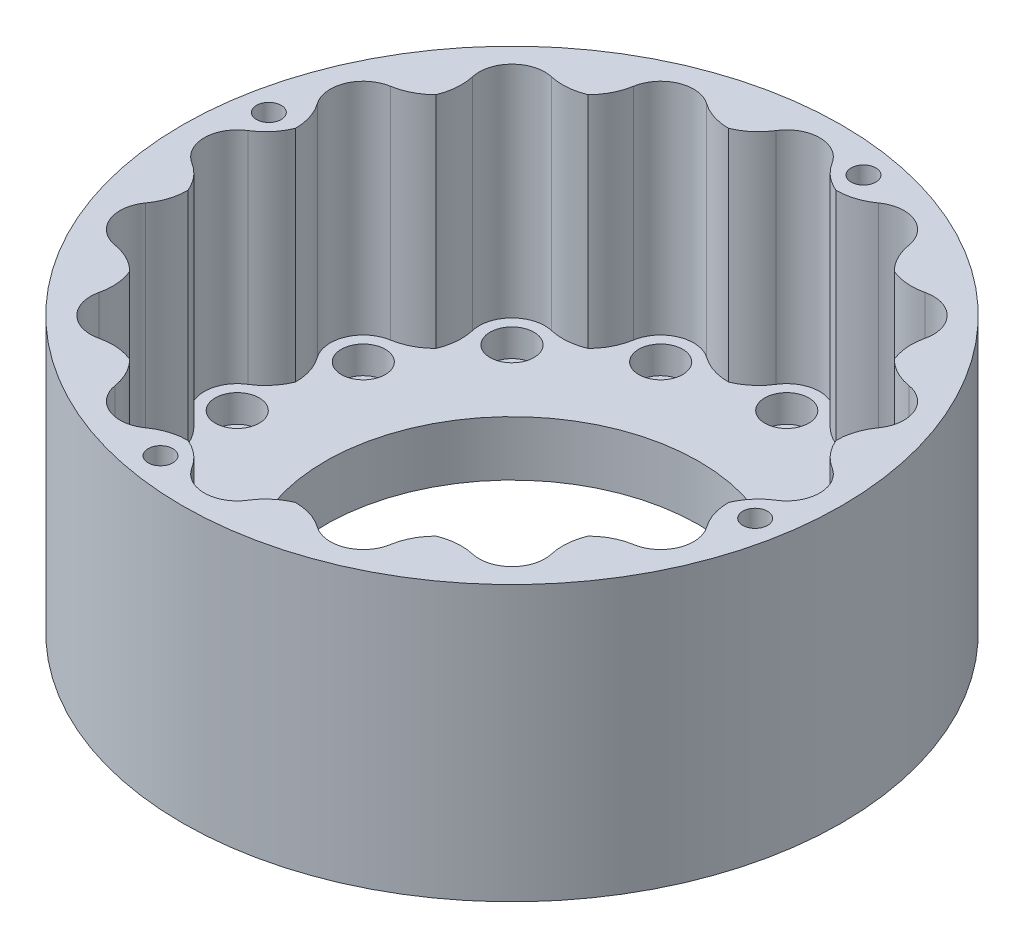
SolidWorks part; units mm, degrees
ref_plane "Front Plane" through (0, 0, 0) normal (0, 0, 1) x (1, 0, 0)
ref_plane "Top Plane" through (0, 0, 0) normal (0, 1, 0) x (1, 0, 0)
ref_plane "Right Plane" through (0, 0, 0) normal (1, 0, 0) x (0, 0, -1)
sketch "Sketch1" plane through (0, 0, 0) normal (0, 1, 0) x (1, 0, 0)
  arc A0 (-50.0283, 13.4631) -> (-51.515, 5.9892) centre (-1.875, 0) ccw
  arc A1 (4.1142, 49.64) -> (-7.8642, 49.64) centre (-1.875, 50) ccw
  arc A2 (-16.6515, 42.0695) -> (-16.6233, 42.0995) centre (-21.0092, 46.194) ccw
  arc A3 (-32.7408, 39.3358) -> (-41.2108, 30.8658) centre (-37.2303, 35.3553) ccw
  arc A4 (-45.4444, 24.5297) -> (-50.0283, 13.4631) centre (-48.069, 19.1342) ccw
  arc A5 (-51.515, 5.9892) -> (-51.515, -5.9892) centre (-51.875, 0) ccw
  arc A6 (-50.0283, -13.4631) -> (-45.4444, -24.5297) centre (-48.069, -19.1342) ccw
  arc A7 (-41.2108, -30.8658) -> (-32.7408, -39.3358) centre (-37.2303, -35.3553) ccw
  arc A8 (-26.4047, -43.5694) -> (-15.3381, -48.1533) centre (-21.0092, -46.194) ccw
  arc A9 (-7.8642, -49.64) -> (4.1142, -49.64) centre (-1.875, -50) ccw
  arc A10 (11.5881, -48.1533) -> (22.6547, -43.5694) centre (17.2592, -46.194) ccw
  arc A11 (28.9908, -39.3358) -> (37.4608, -30.8658) centre (33.4803, -35.3553) ccw
  arc A12 (40.4731, -14.5288) -> (40.4074, -14.5845) centre (44.319, -19.1342) ccw
  arc A13 (47.765, -5.9892) -> (47.765, 5.9892) centre (48.125, 0) ccw
  arc A14 (40.4074, 14.5845) -> (40.4731, 14.5288) centre (44.319, 19.1342) ccw
  arc A15 (37.4608, 30.8658) -> (28.9908, 39.3358) centre (33.4803, 35.3553) ccw
  arc A16 (22.6547, 43.5694) -> (11.5881, 48.1533) centre (17.2592, 46.194) ccw
  circle A17 centre (-1.875, 0) radius 60
  arc A18 (-41.2108, 30.8658) -> (-45.4444, 24.5297) centre (-1.875, 0) ccw
  arc A19 (-26.4047, 43.5694) -> (-32.7408, 39.3358) centre (-1.875, 0) ccw
  arc A20 (-15.3381, 48.1533) -> (-26.4047, 43.5694) centre (-21.0092, 46.194) ccw
  arc A21 (-7.8642, 49.64) -> (-15.3381, 48.1533) centre (-1.875, 0) ccw
  arc A22 (11.5881, 48.1533) -> (4.1142, 49.64) centre (-1.875, 0) ccw
  arc A23 (28.9908, 39.3358) -> (22.6547, 43.5694) centre (-1.875, 0) ccw
  arc A24 (41.6944, 24.5297) -> (37.4608, 30.8658) centre (-1.875, 0) ccw
  arc A25 (46.2783, 13.4631) -> (41.6944, 24.5297) centre (44.319, 19.1342) ccw
  arc A26 (46.2783, -13.4631) -> (47.765, -5.9892) centre (-1.875, 0) ccw
  arc A27 (41.6944, -24.5297) -> (46.2783, -13.4631) centre (44.319, -19.1342) ccw
  arc A28 (37.4608, -30.8658) -> (41.6944, -24.5297) centre (-1.875, 0) ccw
  arc A29 (-51.515, -5.9892) -> (-50.0283, -13.4631) centre (-1.875, 0) ccw
  arc A30 (-45.4444, -24.5297) -> (-41.2108, -30.8658) centre (-1.875, 0) ccw
  arc A31 (-32.7408, -39.3358) -> (-26.4047, -43.5694) centre (-1.875, 0) ccw
  arc A32 (-15.3381, -48.1533) -> (-7.8642, -49.64) centre (-1.875, 0) ccw
  arc A33 (-16.6233, -42.0995) -> (-16.6515, -42.0695) centre (-21.0092, -46.194) ccw
  arc A34 (4.1142, -49.64) -> (11.5881, -48.1533) centre (-1.875, 0) ccw
  arc A35 (22.6547, -43.5694) -> (28.9908, -39.3358) centre (-1.875, 0) ccw
  arc A36 (47.765, 5.9892) -> (46.2783, 13.4631) centre (-1.875, 0) ccw
  spline S0 degree 4 poles (44.0747, 11.4987) (44.2543, 11.2167) (44.5698, 10.6242) (44.9021, 9.6808) (45.0642, 8.3642) (44.9446, 7.1282) (44.593, 6.0249) (44.1211, 5.1947) (43.695, 4.5754) (43.3564, 4.0472) (43.0998, 3.6163) (42.8821, 3.198) (42.6994, 2.7973) (42.5503, 2.4153) (42.4301, 2.0557) (42.3415, 1.7357) (42.2778, 1.4587) (42.224, 1.1791) (42.1875, 0.9457) (42.1595, 0.7089) (42.1421, 0.4978) (42.1336, 0.3578) (42.1278, 0.2085) (42.1243, 0.037) (42.1247, -0.0678) (42.1293, -0.2634) (42.1379, -0.4367) (42.15, -0.5999) (42.1691, -0.7936) (42.1974, -1.0101) (42.2414, -1.2799) (42.3074, -1.6012) (42.4037, -1.9716) (42.5387, -2.3877) (42.6983, -2.7948) (42.8796, -3.1931) (43.1366, -3.6835) (43.482, -4.2594) (43.9287, -4.9065) (44.4091, -5.6745) (44.8007, -6.6105) (45.0295, -7.7093) (45.0295, -8.9484) (44.7352, -10.2696) (44.1902, -11.4212) (43.4619, -12.3657) (42.6206, -13.0778) (41.7593, -13.602) (40.7824, -14.2408) (39.77, -15.1062) (38.838, -16.2841) (38.1405, -17.7977) (37.8498, -19.2831) (37.8586, -20.6377) (38.0279, -21.8199) (38.2279, -22.8394) (38.2788, -23.9779) (38.0615, -25.1966) (37.5489, -26.4121) (36.7247, -27.5436) (35.7476, -28.3911) (34.706, -28.96) (33.6586, -29.2738) (32.6702, -29.405) (31.5286, -29.5836) (30.2595, -29.9481) (28.9262, -30.6268) (27.659, -31.7106) (26.7717, -32.9447) (26.2118, -34.1914) (25.9145, -35.2243) (25.7304, -35.9895) (25.5039, -36.7438) (25.1586, -37.555) (24.5413, -38.4785) (23.5696, -39.3957) (22.3328, -40.1097) (21.0527, -40.4927) (19.9443, -40.5655) (19.0691, -40.4589) (18.3026, -40.2779) (17.5479, -40.0547) (16.5047, -39.7958) (15.1451, -39.6573) (13.6327, -39.8087) (12.0605, -40.3642) (10.8061, -41.1795) (9.8558, -42.0964) (9.1304, -42.9957) (8.5226, -43.7861) (7.7271, -44.5363) (6.7136, -45.1539) (5.4911, -45.5763) (4.0991, -45.7244) (2.7902, -45.5605) (1.6261, -45.1394) (0.6656, -44.526) (-0.1173, -43.8431) (-1.0565, -43.1053) (-2.2252, -42.4205) (-3.657, -41.9295) (-5.3166, -41.7767) (-6.8026, -41.9949) (-8.0583, -42.439) (-9.1, -42.9656) (-9.9846, -43.4494) (-11.0219, -43.8219) (-12.2041, -43.9805) (-13.4901, -43.8751) (-14.8122, -43.455) (-15.9301, -42.7928) (-16.8127, -41.9651) (-17.4446, -41.0507) (-17.8788, -40.1387) (-18.4163, -39.084) (-19.1877, -37.9587) (-20.2985, -36.882) (-21.7915, -36.02) (-23.2794, -35.5964) (-24.6396, -35.491) (-25.8217, -35.5529) (-26.8286, -35.6328) (-27.9365, -35.5428) (-29.0946, -35.1922) (-30.227, -34.5552) (-31.2519, -33.6204) (-31.9862, -32.5593) (-32.4399, -31.4562) (-32.636, -30.3717) (-32.6594, -29.3636) (-32.7241, -28.1982) (-32.9674, -26.8887) (-33.5214, -25.4926) (-34.4835, -24.1318) (-35.6246, -23.1374) (-36.8021, -22.4676) (-37.9106, -22.0232) (-38.8934, -21.6866) (-39.9049, -21.1614) (-40.8517, -20.3639) (-41.648, -19.3123) (-42.2158, -18.0327) (-42.4612, -16.7628) (-42.4331, -15.5762) (-42.1811, -14.5123) (-41.8006, -13.5907) (-41.3845, -12.5128) (-41.0655, -11.2314) (-40.9867, -9.7374) (-41.2916, -8.0981) (-41.8623, -6.8333) (-42.485, -5.9251) (-43.0125, -5.3085) (-43.3736, -4.9275) (-43.7476, -4.5595) (-44.1231, -4.193) (-44.4829, -3.8105) (-44.8105, -3.3997) (-45.0744, -2.9955) (-45.2825, -2.6081) (-45.444, -2.2456) (-45.5676, -1.9138) (-45.6577, -1.6174) (-45.7221, -1.3598) (-45.7672, -1.1433) (-45.7981, -0.9691) (-45.8239, -0.7941) (-45.8419, -0.6396) (-45.8542, -0.5087) (-45.8622, -0.3996) (-45.8674, -0.31) (-45.8722, -0.1929) (-45.8754, -0.0484) (-45.8754, 0.057) (-45.8707, 0.2539) (-45.8614, 0.4217) (-45.8475, 0.5867) (-45.8289, 0.7543) (-45.8057, 0.9209) (-45.7778, 1.0866) (-45.7208, 1.3751) (-45.6162, 1.7824) (-45.4517, 2.2512) (-45.2056, 2.7679) (-44.9364, 3.2145) (-44.6596, 3.5954) (-44.3529, 3.9526) (-44.0247, 4.2897) (-43.6878, 4.6178) (-43.3537, 4.9489) (-43.036, 5.2844) (-42.7388, 5.6275) (-42.4647, 5.9787) (-42.2147, 6.3375) (-41.9285, 6.8032) (-41.6301, 7.388) (-41.2988, 8.2445) (-41.0869, 9.2182) (-41.0245, 10.1783) (-41.079, 10.9169) (-41.1306, 11.2832) (-41.1623, 11.4653) knots 0 0 0 0 0 0.00752 0.015039 0.022311 0.029582 0.03522 0.040858 0.043677 0.046496 0.049315 0.052134 0.054265 0.056396 0.058526 0.060657 0.061722 0.062788 0.064918 0.065984 0.067049 0.067582 0.068115 0.06918 0.070492 0.071149 0.071805 0.073033 0.074262 0.07549 0.076719 0.079176 0.081633 0.084089 0.086546 0.089003 0.09146 0.096539 0.101618 0.106697 0.111776 0.11923 0.126684 0.134323 0.141963 0.147625 0.153288 0.15895 0.164612 0.173852 0.183092 0.192408 0.201724 0.207559 0.213395 0.219231 0.225067 0.233024 0.240981 0.24862 0.25626 0.261858 0.267455 0.273053 0.278651 0.287828 0.297005 0.30639 0.315776 0.321674 0.327572 0.330521 0.33347 0.339368 0.347323 0.355277 0.363232 0.371186 0.377084 0.380033 0.382982 0.38888 0.394778 0.404164 0.413549 0.422726 0.431904 0.437501 0.443099 0.448697 0.454294 0.461934 0.469574 0.477531 0.485487 0.491323 0.497159 0.502995 0.508831 0.518146 0.527462 0.536702 0.545942 0.551604 0.557267 0.562929 0.568591 0.576231 0.58387 0.591691 0.599511 0.605182 0.610853 0.616525 0.622196 0.631785 0.641374 0.650964 0.660553 0.666224 0.671895 0.677566 0.683238 0.691058 0.698878 0.706518 0.714157 0.71982 0.725482 0.731145 0.736807 0.746047 0.755287 0.764602 0.773918 0.779754 0.78559 0.791426 0.797261 0.805218 0.813175 0.820815 0.828454 0.834052 0.83965 0.845248 0.850845 0.860022 0.869199 0.878585 0.887971 0.89092 0.893869 0.896818 0.899767 0.902716 0.905665 0.908614 0.911563 0.913551 0.91554 0.917528 0.919517 0.920511 0.921506 0.9225 0.923494 0.924489 0.924986 0.925483 0.92598 0.926477 0.927472 0.928416 0.929361 0.930305 0.931249 0.932194 0.933138 0.934083 0.935027 0.938805 0.942583 0.945226 0.947869 0.950513 0.953156 0.955799 0.958442 0.961086 0.963729 0.966185 0.968641 0.971097 0.973554 0.978466 0.983378 0.991689 0.995845 1 1 1 1 1 construction
  spline S1 degree 4 poles (40.4731, -14.5288) (40.4566, -14.5426) (40.4402, -14.5565) (40.4237, -14.5705) (40.4074, -14.5845) knots 0.165033 0.165033 0.165033 0.165033 0.165033 0.165518 0.165518 0.165518 0.165518 0.165518
  spline S2 degree 4 poles (40.4731, 14.5288) (40.4566, 14.5426) (40.4402, 14.5565) (40.4237, 14.5705) (40.4074, 14.5845) knots 0.165033 0.165033 0.165033 0.165033 0.165033 0.165518 0.165518 0.165518 0.165518 0.165518
  spline S3 degree 4 poles (-16.6233, 42.0995) (-16.6304, 42.0921) (-16.6375, 42.0846) (-16.6445, 42.0771) (-16.6515, 42.0695) knots 0.600544 0.600544 0.600544 0.600544 0.600544 0.600775 0.600775 0.600775 0.600775 0.600775
  dimension "D1" = 16
extrude "Boss-Extrude1" add sketch "Sketch1" along normal blind 50 contours A17 | A26 A13 A36 A25 A24 A15 A23 A16 A22 A1 A21 A20 A19 A3 A18 A4 A0 A5 A29 A6 A30 A7 A31 A8 A32 A9 A34 A10 A35 A11 A28 A27
sketch "Sketch3" plane through (0, 0, 0) normal (0, 1, 0) x (1, 0, 0)
  circle A0 centre (-1.875, 0) radius 60
extrude "Boss-Extrude2" add sketch "Sketch3" along normal blind 10
fillet "Fillet1" radius 10 2 edges at (11.5881, 30, -48.1533) (4.1142, 30, -49.64)
fillet "Fillet2" radius 10 30 edges at (-50.0283, 30, -13.4631) (-51.515, 30, -5.9892) (-51.515, 30, 5.9892) (-50.0283, 30, 13.4631) (-45.4444, 30, 24.5297) (-41.2108, 30, 30.8658) (-32.7408, 30, 39.3358) (-26.4047, 30, 43.5694) (-15.3381, 30, 48.1533) (-7.8642, 30, 49.64) (-45.4444, 30, -24.5297) (-41.2108, 30, -30.8658) (-32.7408, 30, -39.3358) (-26.4047, 30, -43.5694) (-7.8642, 30, -49.64) (-15.3381, 30, -48.1533) (4.1142, 30, 49.64) (11.5881, 30, 48.1533) (22.6547, 30, 43.5694) (28.9908, 30, 39.3358) (37.4608, 30, 30.8658) (41.6944, 30, 24.5297) (46.2783, 30, 13.4631) (47.765, 30, 5.9892) (47.765, 30, -5.9892) (46.2783, 30, -13.4631) (41.6944, 30, -24.5297) (37.4608, 30, -30.8658) (28.9908, 30, -39.3358) (22.6547, 30, -43.5694)
sketch "Sketch5" plane through (0, 50, 0) normal (0, 1, 0) x (1, 0, 0)
  circle A0 centre (-11.7359, -54.1088) radius 2.25
  circle A3 centre (-55.9838, 9.8609) radius 2.25
  circle A4 centre (7.9859, 54.1088) radius 2.25
  circle A5 centre (52.2338, -9.8609) radius 2.25
  point P12 (-1.875, 0)
  dimension "D1" = 4
extrude "Cut-Extrude2" cut sketch "Sketch5" against normal blind 6.1 contours A4 | A3 | A0 | A5 region at (7.9859, 50, -54.1088)
sketch "Sketch6" plane through (0, 10, 0) normal (0, 1, 0) x (1, 0, 0)
  circle A0 centre (-1.875, 0) radius 50 construction
  circle A1 centre (-1.875, 50) radius 4
  circle A2 centre (17.2592, 46.194) radius 4
  circle A3 centre (33.4803, 35.3553) radius 4
  circle A4 centre (44.319, 19.1342) radius 4
  circle A5 centre (48.125, 0) radius 4
  circle A6 centre (44.319, -19.1342) radius 4
  circle A7 centre (33.4803, -35.3553) radius 4
  circle A8 centre (17.2592, -46.194) radius 4
  circle A9 centre (-1.875, -50) radius 4
  circle A10 centre (-21.0092, -46.194) radius 4
  circle A11 centre (-37.2303, -35.3553) radius 4
  circle A12 centre (-48.069, -19.1342) radius 4
  circle A13 centre (-51.875, 0) radius 4
  circle A14 centre (-48.069, 19.1342) radius 4
  circle A15 centre (-37.2303, 35.3553) radius 4
  circle A16 centre (-21.0092, 46.194) radius 4
  dimension "D1" = 16
extrude "Cut-Extrude3" cut sketch "Sketch6" against normal blind 5
sketch "Sketch7" plane through (0, 0, 0) normal (0, -1, 0) x (1, 0, 0)
  circle A1 centre (-1.875, 0) radius 34
  point P0 (-1.875, 0)
  dimension "D1" = 68
extrude "Cut-Extrude4" cut sketch "Sketch7" against normal blind 10
sketch "Sketch8" plane through (0, 10, 0) normal (0, 1, 0) x (1, 0, 0)
  circle A0 centre (-37.2303, 35.3553) radius 5.5
